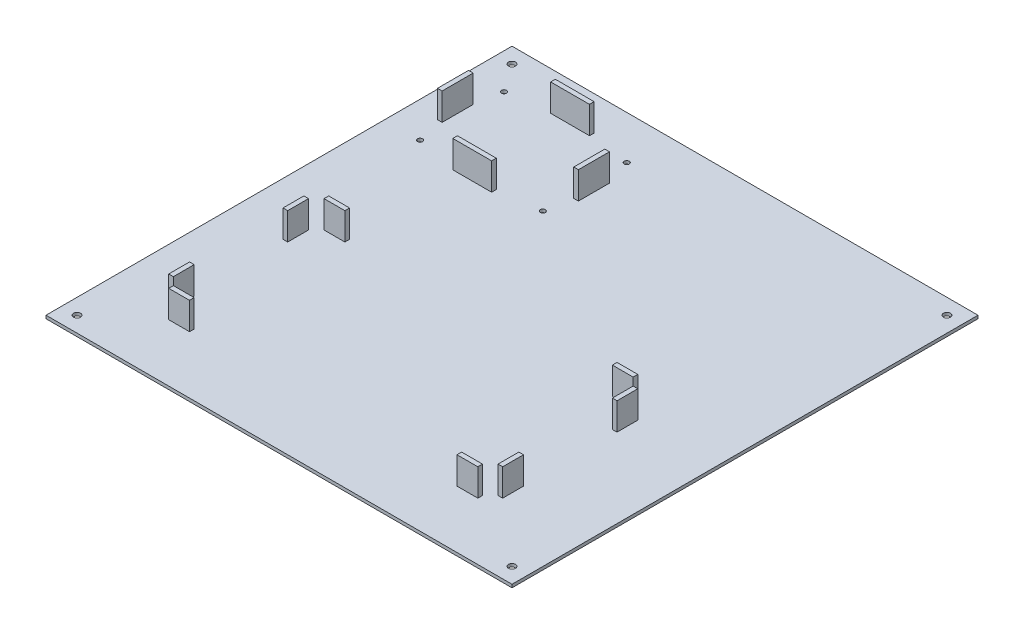
SolidWorks part; units mm, degrees
ref_plane "Front Plane" through (0, 0, 0) normal (0, 0, 1) x (1, 0, 0)
ref_plane "Top Plane" through (0, 0, 0) normal (0, 1, 0) x (1, 0, 0)
ref_plane "Right Plane" through (0, 0, 0) normal (1, 0, 0) x (0, 0, -1)
sketch "Sketch1" plane through (0, 0, 0) normal (0, 1, 0) x (1, 0, 0)
  line L1 (0, 0) -> (600, 0)
  line L2 (0, 0) -> (0, 600)
  line L3 (0, 600) -> (600, 600)
  line L4 (600, 0) -> (600, 600)
  dimension "D1" = 600
  dimension "D2" = 600
extrude "Boss-Extrude1" add sketch "Sketch1" along normal blind 4
sketch "Sketch2" plane through (0, 4, 0) normal (0, 1, 0) x (1, 0, 0)
  line L0 (0, 600) -> (0, 0) construction
  line L2 (600, 600) -> (0, 600) construction
  circle A4 centre (20, 580) radius 4.5
  circle A5 centre (580, 580) radius 4.5
  circle A6 centre (580, 20) radius 4.5
  circle A7 centre (20, 20) radius 4.5
  dimension "D7" = 20
  dimension "D3" = 9
  dimension "D1" = 20
  dimension "D2" = 20
  dimension "D4" = 2
  dimension "D5" = 2
  dimension "D6" = 580
extrude "Cut-Extrude1" cut sketch "Sketch2" against normal up to next
sketch "Sketch4" plane through (0, 4, 0) normal (0, 1, 0) x (1, 0, 0)
  line L0 (0, 600) -> (0, 0) construction
  line L1 (124.75, 550) -> (124.75, 600) construction
  line L2 (40, 550) -> (209.5, 550) construction
  line L3 (40, 550) -> (40, 430) construction
  line L4 (40, 430) -> (209.5, 430) construction
  line L5 (209.5, 550) -> (209.5, 430) construction
  line L6 (600, 600) -> (0, 600) construction
  line L7 (47, 430) -> (47, 424) construction
  line L8 (40, 437) -> (34, 437) construction
  line L9 (202.5, 550) -> (202.5, 556) construction
  line L10 (209.5, 543) -> (215.5, 543) construction
  line L11 (215.5, 556) -> (215.5, 424) construction
  line L12 (215.5, 424) -> (34, 424) construction
  line L13 (34, 424) -> (34, 556) construction
  line L14 (34, 556) -> (215.5, 556) construction
  line L15 (34, 470) -> (34, 510)
  line L16 (99.75, 556) -> (149.75, 556)
  line L17 (40, 470) -> (40, 510)
  line L18 (209.5, 470) -> (209.5, 510)
  line L19 (215.5, 470) -> (215.5, 510)
  line L20 (99.75, 424) -> (149.75, 424)
  line L21 (99.75, 550) -> (149.75, 550)
  line L22 (99.75, 430) -> (149.75, 430)
  line L23 (34, 510) -> (40, 510)
  line L24 (40, 470) -> (34, 470)
  line L25 (99.75, 556) -> (99.75, 550)
  line L26 (149.75, 550) -> (149.75, 556)
  line L27 (209.5, 510) -> (215.5, 510)
  line L28 (215.5, 470) -> (209.5, 470)
  line L29 (149.75, 430) -> (149.75, 424)
  line L30 (99.75, 424) -> (99.75, 430)
  line L31 (203.75, 544) -> (45.75, 544) construction
  line L32 (124.75, 436) -> (124.75, 544) construction
  line L33 (45.75, 436) -> (203.75, 436) construction
  circle A0 centre (79.5, 580) radius 4 construction
  circle A1 centre (45.75, 544) radius 3.25
  circle A2 centre (203.75, 544) radius 3.25
  circle A3 centre (45.75, 436) radius 3.25
  circle A4 centre (203.75, 436) radius 3.25
  point P22 (202.5, 553)
  point P28 (34, 490)
  point P31 (124.75, 556)
  point P34 (40, 490)
  point P37 (209.5, 490)
  point P40 (215.5, 490)
  point P43 (124.75, 424)
  point P46 (124.75, 550)
  point P49 (124.75, 430)
  point P56 (124.75, 490)
  point P58 (124.75, 436)
  point P59 (124.75, 544)
  dimension "D23" = 6.5
  dimension "D24" = 6.5
  dimension "D25" = 6.5
  dimension "D26" = 6.5
  dimension "D1" = 169.5
  dimension "D2" = 120
  dimension "D3" = 50
  dimension "D4" = 40
  dimension "D5" = 6
  dimension "D6" = 6
  dimension "D7" = 6
  dimension "D8" = 6
  dimension "D9" = 6
  dimension "D10" = 13
  dimension "D11" = 13
  dimension "D12" = 13
  dimension "D13" = 13
  dimension "D14" = 40
  dimension "D15" = 50
  dimension "D16" = 50
  dimension "D17" = 40
  dimension "D18" = 158
  dimension "D19" = 5.75
  dimension "D20" = 108
  dimension "D21" = 6
  dimension "D22" = 158
extrude "Cut-Extrude2" cut sketch "Sketch4" against normal up to next contours A1 | A3 | A4 | A2 region at (45.75, 4, -544) region at (203.75, 4, -544) region at (45.75, 4, -436) region at (203.75, 4, -436)
extrude "Boss-Extrude2" add sketch "Sketch4<3>" along normal blind 35 contours L21 L26 L16 L25 | L24 L17 L23 L15 | L28 L19 L27 L18 | L30 L20 L29 L22 region at (37, 4, -490) region at (124.75, 4, -553) region at (212.5, 4, -490) region at (124.75, 4, -427)
sketch "Sketch4<3>" plane through (0, 4, 0) normal (0, 1, 0) x (1, 0, 0) same geometry as "Sketch4"
sketch "Sketch5" plane through (0, 4, 0) normal (0, 1, 0) x (1, 0, 0)
  line L0 (74, 177) -> (492, 177) construction
  line L1 (492, 90) -> (492, 116.8)
  line L2 (300, 600) -> (300, 0) construction
  line L3 (600, 600) -> (0, 600) construction
  line L4 (492, 80) -> (492, 90) construction
  line L5 (0, 0) -> (600, 0) construction
  line L6 (0, 300) -> (600, 300) construction
  line L7 (0, 600) -> (0, 0) construction
  line L8 (600, 0) -> (600, 600) construction
  line L9 (283, 80) -> (283, 274) construction
  line L10 (74, 274) -> (68, 274) construction
  line L11 (84, 274) -> (110.8, 274)
  line L12 (74, 264) -> (74, 237.2)
  line L13 (84, 80) -> (110.8, 80)
  line L14 (492, 264) -> (492, 237.2)
  line L15 (74, 274) -> (74, 280) construction
  line L16 (492, 80) -> (498, 80) construction
  line L17 (492, 80) -> (492, 74) construction
  line L18 (492, 90) -> (498, 90)
  line L19 (492, 116.8) -> (498, 116.8)
  line L20 (68, 280) -> (68, 274) construction
  line L21 (84, 74) -> (110.8, 74)
  line L22 (498, 74) -> (498, 80) construction
  line L23 (482, 280) -> (455.2, 280)
  line L24 (492, 264) -> (492, 237.2)
  line L25 (492, 274) -> (492, 264) construction
  line L26 (492, 264) -> (498, 264)
  line L27 (492, 237.2) -> (498, 237.2)
  line L28 (74, 237.2) -> (68, 237.2)
  line L29 (74, 264) -> (68, 264)
  line L30 (74, 90) -> (68, 90)
  line L31 (74, 116.8) -> (68, 116.8)
  line L32 (84, 274) -> (84, 280)
  line L33 (84, 80) -> (84, 74)
  line L34 (110.8, 274) -> (110.8, 280)
  line L35 (110.8, 80) -> (110.8, 74)
  line L36 (455.2, 80) -> (455.2, 74)
  line L37 (482, 80) -> (482, 74)
  line L38 (455.2, 274) -> (455.2, 280)
  line L39 (482, 274) -> (482, 280)
  line L40 (300, 280) -> (110.8, 280) construction
  line L41 (110.8, 280) -> (84, 280)
  line L42 (110.8, 274) -> (283, 274) construction
  line L43 (283, 274) -> (300, 274) construction
  line L44 (455.2, 280) -> (300, 280) construction
  line L45 (300, 274) -> (455.2, 274) construction
  line L46 (455.2, 274) -> (482, 274)
  line L47 (482, 274) -> (492, 274) construction
  line L48 (498, 280) -> (482, 280) construction
  line L49 (498, 264) -> (498, 280) construction
  line L50 (492, 274) -> (492, 264) construction
  line L51 (492, 274) -> (492, 264) construction
  line L52 (84, 280) -> (74, 280) construction
  line L53 (74, 280) -> (68, 280) construction
  line L54 (74, 274) -> (84, 274) construction
  line L55 (74, 274) -> (74, 264) construction
  line L56 (68, 274) -> (68, 264) construction
  line L57 (68, 264) -> (68, 237.2)
  line L58 (68, 74) -> (84, 74) construction
  line L59 (74, 80) -> (84, 80) construction
  line L60 (74, 90) -> (74, 80) construction
  line L61 (68, 90) -> (68, 74) construction
  line L62 (68, 237.2) -> (68, 116.8) construction
  line L63 (68, 116.8) -> (68, 90)
  line L64 (74, 177) -> (74, 116.8) construction
  line L65 (74, 116.8) -> (74, 90)
  line L66 (74, 237.2) -> (74, 177) construction
  line L67 (110.8, 80) -> (283, 80) construction
  line L68 (283, 80) -> (300, 80) construction
  line L69 (110.8, 74) -> (300, 74) construction
  line L70 (455.2, 74) -> (482, 74)
  line L71 (300, 74) -> (455.2, 74) construction
  line L72 (300, 80) -> (455.2, 80) construction
  line L73 (455.2, 80) -> (482, 80)
  line L74 (482, 74) -> (492, 74) construction
  line L75 (492, 74) -> (498, 74) construction
  line L76 (482, 80) -> (492, 80) construction
  line L77 (492, 80) -> (492, 90) construction
  line L78 (492, 90) -> (492, 80) construction
  line L79 (498, 80) -> (498, 90) construction
  line L80 (498, 90) -> (498, 116.8)
  line L81 (498, 116.8) -> (498, 237.2) construction
  line L82 (498, 237.2) -> (498, 264)
  line L83 (492, 177) -> (492, 116.8) construction
  line L84 (492, 116.8) -> (492, 90)
  line L85 (492, 237.2) -> (492, 177) construction
  dimension "D1" = 68
  dimension "D2" = 74
  dimension "D3" = 84
  dimension "D4" = 110.8
  dimension "D5" = 283
  dimension "D6" = 455.2
  dimension "D7" = 74
  dimension "D8" = 177
extrude "Boss-Extrude3" add sketch "Sketch5" along normal blind 35 contours L29 L57 L28 L12 | L38 L46 L39 L23 | L27 L82 L26 L14 | L18 L80 L19 L1 | L73 L36 L70 L37 | L11 L34 L41 L32 | L65 L30 L63 L31 | L13 L35 L21 L33 region at (495, 4, -103.4) region at (71, 4, -250.6) region at (495, 4, -250.6) region at (468.6, 4, -277) region at (468.6, 4, -77)
